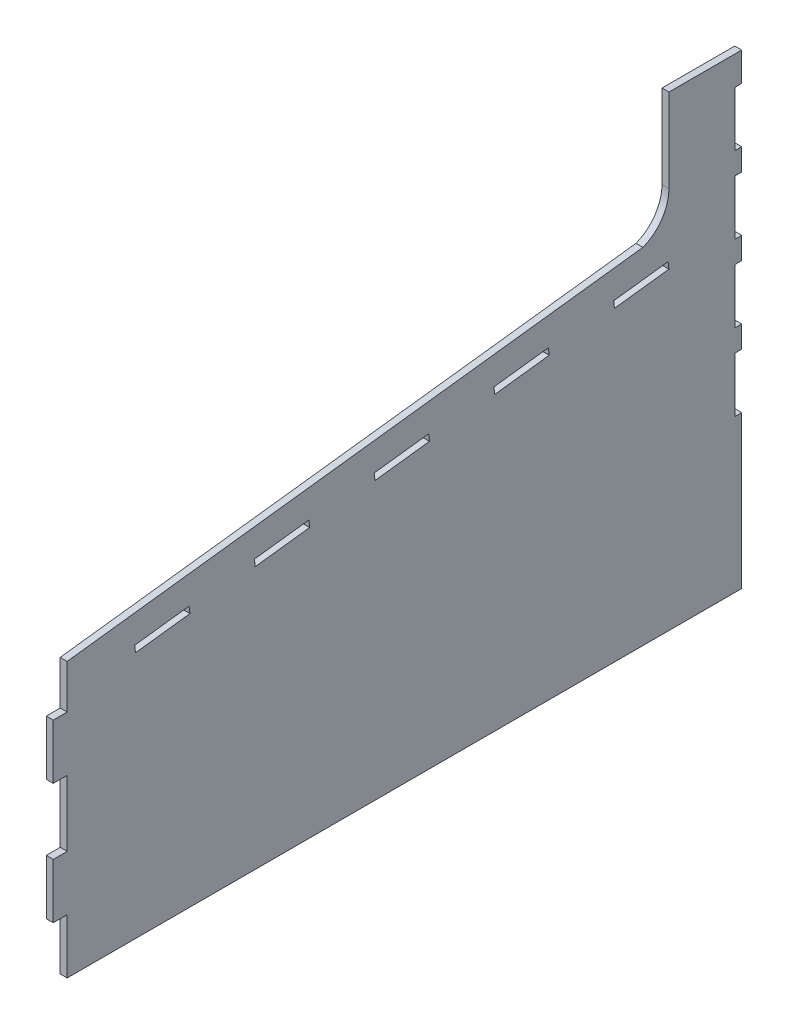
SolidWorks part; units mm, degrees
material "Beech"
ref_plane "Front Plane" through (0, 0, 0) normal (0, 0, 1) x (1, 0, 0)
ref_plane "Top Plane" through (0, 0, 0) normal (0, 1, 0) x (1, 0, 0)
ref_plane "Right Plane" through (0, 0, 0) normal (1, 0, 0) x (0, 0, -1)
sketch "Sketch1" plane through (0, 0, 0) normal (1, 0, 0) x (0, 0, -1)
  line L0 (0, 250) -> (524.9325, 314.4536)
  line L1 (0, 0) -> (615, 0)
  line L2 (0, 0) -> (0, 50)
  line L4 (615, 0) -> (615, 138.97)
  line L6 (615, 258.9358) -> (615, 278.9015)
  line L7 (615, 425.2173) -> (548.65, 425.2173)
  line L8 (548.65, 348.9873) -> (548.65, 425.2173)
  line L9 (0, 250) -> (609, 250) construction
  line L10 (524.9325, 314.4536) -> (615, 325.5125) construction
  line L11 (-12.7, 160) -> (-12.7, 210)
  line L12 (0, 50) -> (-12.7, 50)
  line L14 (0, 100) -> (-12.7, 100)
  line L15 (-12.7, 50) -> (-12.7, 100)
  line L16 (0, 160) -> (-12.7, 160)
  line L18 (0, 210) -> (-12.7, 210)
  line L19 (0, 210) -> (0, 250)
  line L21 (0, 100) -> (0, 160)
  line L23 (615, 398.8673) -> (608.65, 398.8673)
  line L25 (615, 348.8673) -> (608.65, 348.8673)
  line L26 (608.65, 398.8673) -> (608.65, 348.8673)
  line L28 (615, 328.9015) -> (608.65, 328.9015)
  line L29 (608.65, 328.9015) -> (608.65, 278.9015)
  line L30 (615, 278.9015) -> (608.65, 278.9015)
  line L32 (615, 258.9358) -> (608.65, 258.9358)
  line L33 (608.65, 258.9358) -> (608.65, 208.9358)
  line L34 (615, 208.9358) -> (608.65, 208.9358)
  line L36 (615, 188.97) -> (608.65, 188.97)
  line L37 (608.65, 188.97) -> (608.65, 138.97)
  line L38 (615, 138.97) -> (608.65, 138.97)
  line L39 (615, 188.97) -> (615, 208.9358)
  line L42 (615, 328.9015) -> (615, 348.8673)
  line L44 (615, 398.8673) -> (615, 425.2173)
  arc A0 (524.9325, 314.4536) -> (548.65, 348.9873) centre (511.65, 348.9873) ccw
  dimension "D4" = 37
  dimension "D1" = 615
  dimension "D2" = 250
  dimension "D3" = 66.35
  dimension "D5" = 7
  dimension "D6" = 175.32
  dimension "D7" = 76.23
  dimension "D8" = 12.7
  dimension "D9" = 50
  dimension "D10" = 50
  dimension "D11" = 2
  dimension "D12" = 40
  dimension "D13" = 6.35
  dimension "D14" = 50
  dimension "D15" = 26.35
  dimension "D17" = 138.97
  dimension "D16" = 4
extrude "Boss-Extrude1" add sketch "Sketch1" along normal blind 6.35
sketch "Sketch2" plane through (6.35, 0, 0) normal (1, 0, 0) x (0, 0, -1)
  line L0 (524.9325, 314.4536) -> (615, 325.5125) construction
  line L1 (615, 0) -> (615, 138.97) construction
  line L2 (524.9325, 314.4536) -> (0, 250) construction
  line L3 (0, 224.4093) -> (615, 299.9218) construction
  line L4 (0, 50) -> (0, 0) construction
  line L5 (61.5379, 231.9651) -> (62.3117, 225.6625)
  line L6 (62.3117, 225.6625) -> (111.939, 231.7559)
  line L7 (111.939, 231.7559) -> (111.1652, 238.0586)
  line L8 (111.1652, 238.0586) -> (61.5379, 231.9651)
  line L9 (220.3452, 251.4642) -> (170.7179, 245.3708)
  line L10 (170.7179, 245.3708) -> (171.4918, 239.0681)
  line L11 (171.4918, 239.0681) -> (221.1191, 245.1616)
  line L12 (221.1191, 245.1616) -> (220.3452, 251.4642)
  line L13 (329.5253, 264.8699) -> (279.898, 258.7764)
  line L14 (279.898, 258.7764) -> (280.6719, 252.4737)
  line L15 (280.6719, 252.4737) -> (330.2992, 258.5672)
  line L16 (330.2992, 258.5672) -> (329.5253, 264.8699)
  line L17 (438.7054, 278.2755) -> (389.0781, 272.182)
  line L18 (389.0781, 272.182) -> (389.852, 265.8794)
  line L19 (389.852, 265.8794) -> (439.4793, 271.9728)
  line L20 (439.4793, 271.9728) -> (438.7054, 278.2755)
  line L21 (547.8855, 291.6811) -> (498.2582, 285.5877)
  line L22 (498.2582, 285.5877) -> (499.032, 279.285)
  line L23 (499.032, 279.285) -> (548.6593, 285.3785)
  line L24 (548.6593, 285.3785) -> (547.8855, 291.6811)
  dimension "D1" = 25.4
  dimension "D2" = 50
  dimension "D3" = 6.35
  dimension "D4" = 62
extrude "Cut-Extrude1" cut sketch "Sketch2" against normal blind 6.35
